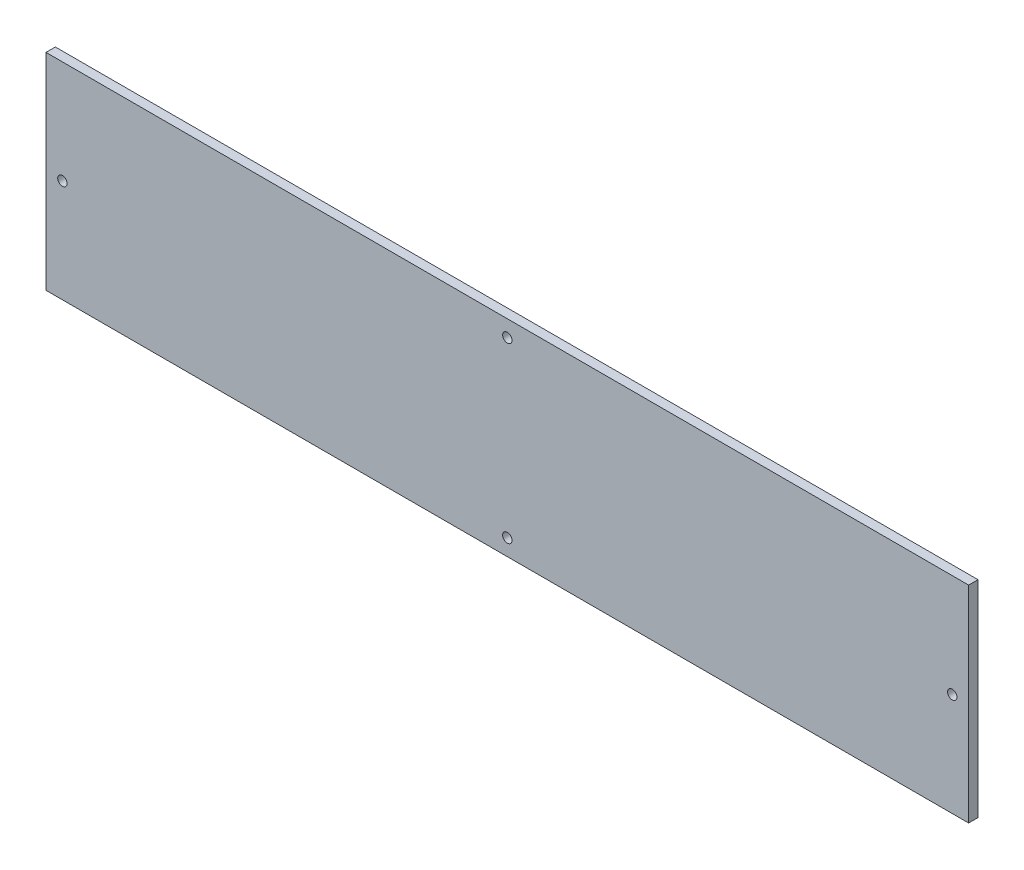
SolidWorks part; units mm, degrees
ref_plane "Piano frontale" through (0, 0, 0) normal (0, 0, 1) x (1, 0, 0)
ref_plane "Piano superiore" through (0, 0, 0) normal (0, 1, 0) x (1, 0, 0)
ref_plane "Piano destro" through (0, 0, 0) normal (1, 0, 0) x (0, 0, -1)
sketch "Schizzo1" plane through (0, 0, 0) normal (0, 0, 1) x (1, 0, 0)
  line L0 (-197, 351.6275) -> (-197, -66.2585) construction
  line L1 (0, 0) -> (-394, 0)
  line L2 (0, 0) -> (0, 88)
  line L3 (0, 88) -> (-394, 88)
  line L4 (-394, 0) -> (-394, 88)
  line L5 (-387.9788, 44) -> (120.8821, 44) construction
  circle A1 centre (-7, 44) radius 2
  circle A2 centre (-197, 81) radius 2
  circle A3 centre (-387, 44) radius 2
  circle A4 centre (-197, 7) radius 2
  point P9 (-197, 44)
  dimension "D3" = 4
  dimension "D1" = 394
  dimension "314" = 88
  dimension "D4" = 7
  dimension "D6" = 7
extrude "Estrusione-Estrusione1" add sketch "Schizzo1" along normal blind 4
